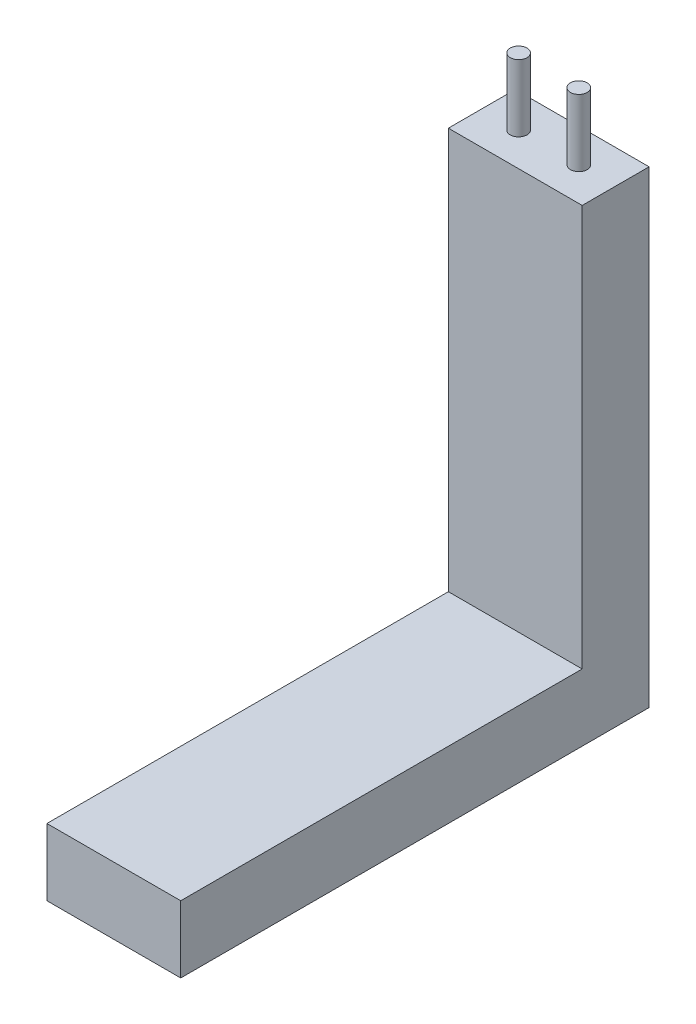
SolidWorks part; units mm, degrees
ref_plane "Front Plane" through (0, 0, 0) normal (0, 0, 1) x (1, 0, 0)
ref_plane "Top Plane" through (0, 0, 0) normal (0, 1, 0) x (1, 0, 0)
ref_plane "Right Plane" through (0, 0, 0) normal (1, 0, 0) x (0, 0, -1)
sketch "Sketch3" plane through (0, 0, 0) normal (0, 1, 0) x (1, 0, 0)
  line L0 (-25.4, 0) -> (25.4, 0)
  line L1 (-25.4, 0) -> (-25.4, 25.4)
  line L2 (-25.4, 25.4) -> (25.4, 25.4)
  line L3 (25.4, 25.4) -> (25.4, 0)
extrude "Boss-Extrude1" add sketch "Sketch3" along normal blind 177.8
sketch "Sketch5" plane through (0, 0, 0) normal (0, 0, 1) x (1, 0, 0)
  line L0 (25.4, 177.8) -> (25.4, 0) construction
  line L1 (-25.4, 0) -> (25.4, 0)
  line L2 (-25.4, 0) -> (-25.4, 25.4)
  line L3 (-25.4, 25.4) -> (25.4, 25.4)
  line L4 (25.4, 0) -> (25.4, 25.4)
extrude "Boss-Extrude3" add sketch "Sketch5" along normal blind 152.4 contours L3 L4 L1 L2
sketch "Sketch6" plane through (0, 177.8, 0) normal (0, 1, 0) x (1, 0, 0)
  line L0 (0, 25.4) -> (0, 0) construction
  line L1 (25.4, 25.4) -> (-25.4, 25.4) construction
  line L2 (-25.4, 0) -> (25.4, 0) construction
  line L3 (0, 12.7) -> (11.43, 12.7) construction
  line L4 (0, 12.7) -> (-11.43, 12.7) construction
  circle A0 centre (-11.43, 12.7) radius 3.175
  circle A1 centre (11.43, 12.7) radius 3.175
  dimension "D1" = 6.35
  dimension "D2" = 6.35
extrude "Boss-Extrude4" add sketch "Sketch6" along normal blind 25.4
sketch "Sketch7" plane through (0, 0, 0) normal (0, -1, 0) x (-1, 0, 0)
  line L0 (0, 25.4) -> (0, 0) construction
  line L1 (-25.4, 25.4) -> (25.4, 25.4) construction
  line L2 (0, 12.7) -> (-11.43, 12.7) construction
  line L3 (0, 12.7) -> (11.43, 12.7) construction
  circle A0 centre (-11.43, 12.7) radius 5.207
  circle A1 centre (11.43, 12.7) radius 5.207
  dimension "D1" = 10.414
  dimension "D2" = 10.414
extrude "Cut-Extrude1" cut sketch "Sketch7" against normal blind 17.78
